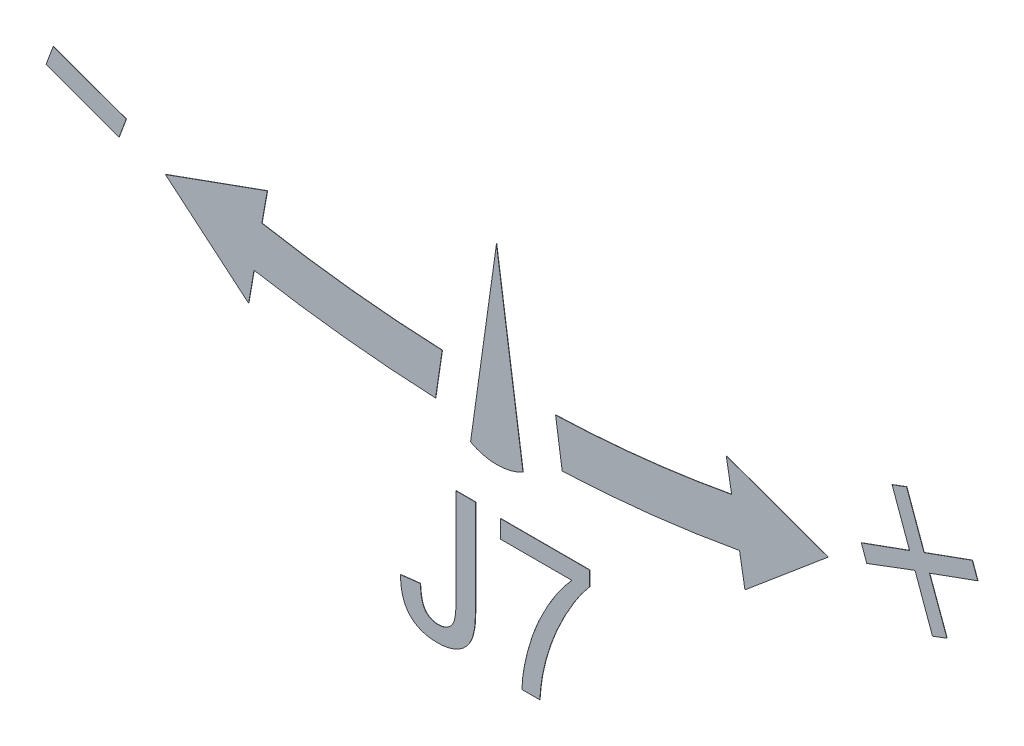
SolidWorks part; units mm, degrees
material "Air"
ref_plane "Front" through (0, 0, 0) normal (0, 0, 1) x (1, 0, 0)
ref_plane "Top" through (0, 0, 0) normal (0, 1, 0) x (1, 0, 0)
ref_plane "Right" through (0, 0, 0) normal (1, 0, 0) x (0, 0, -1)
sketch "Sketch1" plane through (0, 0, 0) normal (0, 0, 1) x (1, 0, 0)
  line L1616 (4481.7115, 1822.0394) -> (4481.7115, 1905.9102)
  line L1617 (4447.8406, 1780.6416) -> (4455.9051, 1781.1792)
  line L1618 (4455.9051, 1781.1792) -> (4464.5072, 1783.8674)
  line L1619 (4464.5072, 1783.8674) -> (4471.4964, 1788.7061)
  line L1620 (4471.4964, 1788.7061) -> (4476.8728, 1795.6953)
  line L1621 (4476.8728, 1795.6953) -> (4480.0986, 1803.7598)
  line L1622 (4480.0986, 1803.7598) -> (4481.1738, 1812.8996)
  line L1623 (4481.1738, 1812.8996) -> (4481.7115, 1822.0394)
  line L1624 (4415.0449, 1816.663) -> (4415.5826, 1809.1362)
  line L1625 (4415.5826, 1809.1362) -> (4416.6578, 1801.0717)
  line L1626 (4416.6578, 1801.0717) -> (4419.8836, 1794.0824)
  line L1627 (4419.8836, 1794.0824) -> (4424.7223, 1788.1685)
  line L1628 (4424.7223, 1788.1685) -> (4431.7116, 1783.8674)
  line L1629 (4431.7116, 1783.8674) -> (4439.2384, 1781.1792)
  line L1630 (4439.2384, 1781.1792) -> (4447.8406, 1780.6416)
  line L1631 (4432.2492, 1818.8136) -> (4415.0449, 1816.663)
  line L1632 (4448.3782, 1794.6201) -> (4444.0771, 1795.1577)
  line L1633 (4444.0771, 1795.1577) -> (4440.3137, 1796.7706)
  line L1634 (4440.3137, 1796.7706) -> (4437.6255, 1799.4588)
  line L1635 (4437.6255, 1799.4588) -> (4435.475, 1802.6846)
  line L1636 (4435.475, 1802.6846) -> (4433.3245, 1810.7491)
  line L1637 (4433.3245, 1810.7491) -> (4432.2492, 1818.8136)
  line L1638 (4463.9696, 1820.9641) -> (4463.9696, 1815.0501)
  line L1639 (4463.9696, 1815.0501) -> (4463.4319, 1809.1362)
  line L1640 (4463.4319, 1809.1362) -> (4462.3567, 1803.7598)
  line L1641 (4462.3567, 1803.7598) -> (4459.6685, 1799.9964)
  line L1642 (4459.6685, 1799.9964) -> (4456.4427, 1797.3082)
  line L1643 (4456.4427, 1797.3082) -> (4452.6793, 1795.1577)
  line L1644 (4452.6793, 1795.1577) -> (4448.3782, 1794.6201)
  line L1645 (4463.9696, 1905.9102) -> (4463.9696, 1820.9641)
  line L1646 (4481.7115, 1905.9102) -> (4463.9696, 1905.9102)
  line L1647 (4583.3242, 1891.3941) -> (4583.3242, 1904.2973)
  line L1648 (4544.0769, 1815.5878) -> (4552.1414, 1838.706)
  line L1649 (4552.1414, 1838.706) -> (4562.3565, 1860.2113)
  line L1650 (4562.3565, 1860.2113) -> (4572.0339, 1876.3403)
  line L1651 (4572.0339, 1876.3403) -> (4583.3242, 1891.3941)
  line L1652 (4538.7006, 1782.2545) -> (4540.8511, 1801.0717)
  line L1653 (4540.8511, 1801.0717) -> (4544.0769, 1815.5878)
  line L1654 (4523.1092, 1782.2545) -> (4538.7006, 1782.2545)
  line L1655 (4567.1952, 1888.7059) -> (4553.7543, 1870.964)
  line L1656 (4553.7543, 1870.964) -> (4543.0017, 1852.1468)
  line L1657 (4543.0017, 1852.1468) -> (4533.8619, 1832.2544)
  line L1658 (4533.8619, 1832.2544) -> (4528.4856, 1816.1254)
  line L1659 (4528.4856, 1816.1254) -> (4524.7221, 1799.4588)
  line L1660 (4524.7221, 1799.4588) -> (4523.1092, 1782.2545)
  line L1661 (4503.7544, 1888.7059) -> (4567.1952, 1888.7059)
  line L1662 (4503.7544, 1904.2973) -> (4503.7544, 1888.7059)
  line L1663 (4583.3242, 1904.2973) -> (4503.7544, 1904.2973)
  line L1664 (4098.3789, 2051.6088) -> (4163.4325, 2027.9529)
  line L1665 (4104.8305, 2068.8131) -> (4098.3789, 2051.6088)
  line L1666 (4169.8841, 2045.1572) -> (4104.8305, 2068.8131)
  line L1667 (4163.4325, 2027.9529) -> (4169.8841, 2045.1572)
  line L1668 (4852.6785, 2104.2969) -> (4868.2698, 2061.2862)
  line L1669 (4865.5817, 2109.1356) -> (4852.6785, 2104.2969)
  line L1670 (4881.173, 2066.1249) -> (4865.5817, 2109.1356)
  line L1671 (4924.1837, 2081.7163) -> (4881.173, 2066.1249)
  line L1672 (4929.0224, 2068.2754) -> (4924.1837, 2081.7163)
  line L1673 (4886.0117, 2052.6841) -> (4929.0224, 2068.2754)
  line L1674 (4901.6031, 2010.211) -> (4886.0117, 2052.6841)
  line L1675 (4888.6999, 2005.3723) -> (4901.6031, 2010.211)
  line L1676 (4873.1085, 2048.383) -> (4888.6999, 2005.3723)
  line L1677 (4830.0979, 2032.254) -> (4873.1085, 2048.383)
  line L1678 (4825.2592, 2045.6948) -> (4830.0979, 2032.254)
  line L1679 (4868.2698, 2061.2862) -> (4825.2592, 2045.6948)
  line L1680 (4476.8728, 1949.4585) -> (4477.4104, 1948.9208)
  line L1681 (4477.4104, 1948.9208) -> (4477.948, 1948.9208)
  line L1682 (4477.948, 1948.9208) -> (4478.4857, 1948.3832)
  line L1683 (4478.4857, 1948.3832) -> (4479.5609, 1948.3832)
  line L1684 (4479.5609, 1948.3832) -> (4480.0986, 1947.8456)
  line L1685 (4480.0986, 1947.8456) -> (4480.6362, 1947.8456)
  line L1686 (4480.6362, 1947.8456) -> (4481.1738, 1947.3079)
  line L1687 (4481.1738, 1947.3079) -> (4481.7115, 1947.3079)
  line L1688 (4481.7115, 1947.3079) -> (4482.7867, 1946.7703)
  line L1689 (4482.7867, 1946.7703) -> (4483.862, 1946.7703)
  line L1690 (4483.862, 1946.7703) -> (4484.3996, 1946.2327)
  line L1691 (4484.3996, 1946.2327) -> (4485.4749, 1946.2327)
  line L1692 (4485.4749, 1946.2327) -> (4486.0125, 1945.695)
  line L1693 (4486.0125, 1945.695) -> (4487.0878, 1945.695)
  line L1694 (4487.0878, 1945.695) -> (4487.6254, 1945.1574)
  line L1695 (4487.6254, 1945.1574) -> (4489.2383, 1945.1574)
  line L1696 (4489.2383, 1945.1574) -> (4489.776, 1944.6198)
  line L1697 (4489.776, 1944.6198) -> (4492.4641, 1944.6198)
  line L1698 (4492.4641, 1944.6198) -> (4493.0018, 1944.0821)
  line L1699 (4493.0018, 1944.0821) -> (4506.4426, 1944.0821)
  line L1700 (4506.4426, 1944.0821) -> (4506.9802, 1944.6198)
  line L1701 (4506.9802, 1944.6198) -> (4509.1308, 1944.6198)
  line L1702 (4509.1308, 1944.6198) -> (4510.206, 1945.1574)
  line L1703 (4510.206, 1945.1574) -> (4511.8189, 1945.1574)
  line L1704 (4511.8189, 1945.1574) -> (4512.3566, 1945.695)
  line L1705 (4512.3566, 1945.695) -> (4513.4318, 1945.695)
  line L1706 (4513.4318, 1945.695) -> (4513.9695, 1946.2327)
  line L1707 (4513.9695, 1946.2327) -> (4515.0447, 1946.2327)
  line L1708 (4515.0447, 1946.2327) -> (4515.5824, 1946.7703)
  line L1709 (4515.5824, 1946.7703) -> (4516.6576, 1946.7703)
  line L1710 (4516.6576, 1946.7703) -> (4517.1953, 1947.3079)
  line L1711 (4517.1953, 1947.3079) -> (4517.7329, 1947.3079)
  line L1712 (4517.7329, 1947.3079) -> (4518.2705, 1947.8456)
  line L1713 (4518.2705, 1947.8456) -> (4519.3458, 1947.8456)
  line L1714 (4519.3458, 1947.8456) -> (4519.8834, 1948.3832)
  line L1715 (4519.8834, 1948.3832) -> (4520.4211, 1948.3832)
  line L1716 (4520.4211, 1948.3832) -> (4520.9587, 1948.9208)
  line L1717 (4520.9587, 1948.9208) -> (4521.4963, 1948.9208)
  line L1718 (4521.4963, 1948.9208) -> (4522.034, 1949.4585)
  line L1719 (4522.034, 1949.4585) -> (4522.5716, 1949.4585)
  line L1720 (4522.5716, 1949.4585) -> (4523.1092, 1949.9961)
  line L1721 (4499.991, 2113.9743) -> (4476.8728, 1949.4585)
  line L1722 (4523.6469, 1949.4585) -> (4499.991, 2113.9743)
  line L1723 (4445.69, 1967.738) -> (4451.604, 2007.5229)
  line L1724 (4279.0237, 1957.523) -> (4283.8624, 1985.4799)
  line L1725 (4204.8303, 2019.8884) -> (4279.0237, 1957.523)
  line L1726 (4295.6903, 2052.6841) -> (4204.8303, 2019.8884)
  line L1727 (4290.8516, 2025.2648) -> (4295.6903, 2052.6841)
  line L1728 (4451.604, 2007.5229) -> (4436.5503, 2008.5981)
  line L1729 (4436.5503, 2008.5981) -> (4421.4965, 2009.1358)
  line L1730 (4421.4965, 2009.1358) -> (4406.9804, 2010.211)
  line L1731 (4406.9804, 2010.211) -> (4392.4643, 2011.8239)
  line L1732 (4392.4643, 2011.8239) -> (4377.4106, 2012.8992)
  line L1733 (4377.4106, 2012.8992) -> (4362.8945, 2014.5121)
  line L1734 (4362.8945, 2014.5121) -> (4347.8408, 2016.125)
  line L1735 (4347.8408, 2016.125) -> (4333.3247, 2018.2755)
  line L1736 (4333.3247, 2018.2755) -> (4318.8086, 2020.4261)
  line L1737 (4318.8086, 2020.4261) -> (4304.2925, 2022.5766)
  line L1738 (4304.2925, 2022.5766) -> (4290.314, 2025.2648)
  line L1739 (4283.8624, 1985.4799) -> (4298.9161, 1983.3294)
  line L1740 (4298.9161, 1983.3294) -> (4313.9699, 1980.6412)
  line L1741 (4313.9699, 1980.6412) -> (4329.0236, 1978.4907)
  line L1742 (4329.0236, 1978.4907) -> (4344.0773, 1976.8778)
  line L1743 (4344.0773, 1976.8778) -> (4359.1311, 1974.7272)
  line L1744 (4359.1311, 1974.7272) -> (4374.7224, 1973.1143)
  line L1745 (4374.7224, 1973.1143) -> (4389.7762, 1971.5014)
  line L1746 (4389.7762, 1971.5014) -> (4404.8299, 1970.4262)
  line L1747 (4404.8299, 1970.4262) -> (4420.4213, 1969.3509)
  line L1748 (4420.4213, 1969.3509) -> (4435.475, 1968.2756)
  line L1749 (4435.475, 1968.2756) -> (4445.69, 1968.2756)
  line L1750 (4704.8293, 2052.6841) -> (4709.668, 2025.2648)
  line L1751 (4552.6791, 2008.0605) -> (4558.593, 1967.738)
  line L1752 (4795.6893, 2019.8884) -> (4704.8293, 2052.6841)
  line L1753 (4709.668, 2025.2648) -> (4694.6143, 2023.1142)
  line L1754 (4694.6143, 2023.1142) -> (4680.0982, 2020.9637)
  line L1755 (4680.0982, 2020.9637) -> (4665.5821, 2018.8132)
  line L1756 (4665.5821, 2018.8132) -> (4651.066, 2016.6626)
  line L1757 (4651.066, 2016.6626) -> (4636.0122, 2015.0497)
  line L1758 (4636.0122, 2015.0497) -> (4621.4961, 2013.4368)
  line L1759 (4621.4961, 2013.4368) -> (4606.4424, 2011.8239)
  line L1760 (4606.4424, 2011.8239) -> (4591.9263, 2010.7487)
  line L1761 (4591.9263, 2010.7487) -> (4577.4102, 2009.6734)
  line L1762 (4577.4102, 2009.6734) -> (4562.3565, 2008.5981)
  line L1763 (4562.3565, 2008.5981) -> (4552.6791, 2008.0605)
  line L1764 (4716.6572, 1985.4799) -> (4721.4959, 1957.523)
  line L1765 (4558.593, 1967.738) -> (4573.6468, 1968.8133)
  line L1766 (4573.6468, 1968.8133) -> (4588.7005, 1969.8885)
  line L1767 (4588.7005, 1969.8885) -> (4604.2919, 1970.9638)
  line L1768 (4604.2919, 1970.9638) -> (4619.3456, 1972.5767)
  line L1769 (4619.3456, 1972.5767) -> (4634.3993, 1974.1896)
  line L1770 (4634.3993, 1974.1896) -> (4649.9907, 1975.8025)
  line L1771 (4649.9907, 1975.8025) -> (4665.0444, 1977.4154)
  line L1772 (4665.0444, 1977.4154) -> (4680.0982, 1979.5659)
  line L1773 (4680.0982, 1979.5659) -> (4695.1519, 1982.2541)
  line L1774 (4695.1519, 1982.2541) -> (4710.2056, 1984.4046)
  line L1775 (4710.2056, 1984.4046) -> (4716.6572, 1985.4799)
  line L1776 (4721.4959, 1957.523) -> (4795.6893, 2019.8884)
  line L7984 (4481.7115, 1822.0394) -> (4481.7115, 1905.9102)
  line L7985 (4481.7115, 1905.9102) -> (4463.9696, 1905.9102)
  line L7986 (4463.9696, 1905.9102) -> (4463.9696, 1811.2867)
  line L7987 (4463.9696, 1811.2867) -> (4463.4319, 1809.6738)
  line L7988 (4463.4319, 1809.6738) -> (4463.4319, 1807.5233)
  line L7989 (4463.4319, 1807.5233) -> (4462.8943, 1805.9104)
  line L7990 (4462.8943, 1805.9104) -> (4462.3567, 1804.8351)
  line L7991 (4462.3567, 1804.8351) -> (4462.3567, 1803.7598)
  line L7992 (4462.3567, 1803.7598) -> (4461.819, 1802.6846)
  line L7993 (4461.819, 1802.6846) -> (4461.2814, 1801.6093)
  line L7994 (4461.2814, 1801.6093) -> (4460.7438, 1801.0717)
  line L7995 (4460.7438, 1801.0717) -> (4459.6685, 1799.9964)
  line L7996 (4459.6685, 1799.9964) -> (4459.1309, 1798.9211)
  line L7997 (4459.1309, 1798.9211) -> (4458.5932, 1798.3835)
  line L7998 (4458.5932, 1798.3835) -> (4457.518, 1797.8459)
  line L7999 (4457.518, 1797.8459) -> (4456.4427, 1797.3082)
  line L8000 (4456.4427, 1797.3082) -> (4455.3674, 1796.7706)
  line L8001 (4455.3674, 1796.7706) -> (4454.2922, 1796.233)
  line L8002 (4454.2922, 1796.233) -> (4453.2169, 1795.6953)
  line L8003 (4453.2169, 1795.6953) -> (4452.1416, 1795.1577)
  line L8004 (4452.1416, 1795.1577) -> (4449.4535, 1795.1577)
  line L8005 (4449.4535, 1795.1577) -> (4448.3782, 1794.6201)
  line L8006 (4448.3782, 1794.6201) -> (4447.3029, 1795.1577)
  line L8007 (4447.3029, 1795.1577) -> (4444.6148, 1795.1577)
  line L8008 (4444.6148, 1795.1577) -> (4443.5395, 1795.6953)
  line L8009 (4443.5395, 1795.6953) -> (4442.4642, 1795.6953)
  line L8010 (4442.4642, 1795.6953) -> (4441.389, 1796.233)
  line L8011 (4441.389, 1796.233) -> (4440.3137, 1796.7706)
  line L8012 (4440.3137, 1796.7706) -> (4439.7761, 1797.3082)
  line L8013 (4439.7761, 1797.3082) -> (4438.7008, 1798.3835)
  line L8014 (4438.7008, 1798.3835) -> (4437.6255, 1798.9211)
  line L8015 (4437.6255, 1798.9211) -> (4437.0879, 1799.9964)
  line L8016 (4437.0879, 1799.9964) -> (4436.5503, 1801.0717)
  line L8017 (4436.5503, 1801.0717) -> (4436.0126, 1801.6093)
  line L8018 (4436.0126, 1801.6093) -> (4435.475, 1802.6846)
  line L8019 (4435.475, 1802.6846) -> (4434.9374, 1804.2975)
  line L8020 (4434.9374, 1804.2975) -> (4434.3997, 1805.9104)
  line L8021 (4434.3997, 1805.9104) -> (4433.8621, 1806.9856)
  line L8022 (4433.8621, 1806.9856) -> (4433.3245, 1808.5985)
  line L8023 (4433.3245, 1808.5985) -> (4433.3245, 1810.2114)
  line L8024 (4433.3245, 1810.2114) -> (4432.7868, 1811.8243)
  line L8025 (4432.7868, 1811.8243) -> (4432.7868, 1816.1254)
  line L8026 (4432.7868, 1816.1254) -> (4432.2492, 1818.8136)
  line L8027 (4432.2492, 1818.8136) -> (4415.0449, 1816.663)
  line L8028 (4415.0449, 1816.663) -> (4415.0449, 1809.1362)
  line L8029 (4415.0449, 1809.1362) -> (4415.5826, 1806.9856)
  line L8030 (4415.5826, 1806.9856) -> (4416.1202, 1804.2975)
  line L8031 (4416.1202, 1804.2975) -> (4416.6578, 1801.6093)
  line L8032 (4416.6578, 1801.6093) -> (4417.1955, 1799.4588)
  line L8033 (4417.1955, 1799.4588) -> (4418.2707, 1797.8459)
  line L8034 (4418.2707, 1797.8459) -> (4418.8084, 1795.6953)
  line L8035 (4418.8084, 1795.6953) -> (4419.8836, 1794.0824)
  line L8036 (4419.8836, 1794.0824) -> (4420.9589, 1792.4695)
  line L8037 (4420.9589, 1792.4695) -> (4422.0342, 1790.8566)
  line L8038 (4422.0342, 1790.8566) -> (4423.1094, 1789.2437)
  line L8039 (4423.1094, 1789.2437) -> (4424.7223, 1788.1685)
  line L8040 (4424.7223, 1788.1685) -> (4426.3352, 1786.5556)
  line L8041 (4426.3352, 1786.5556) -> (4427.9481, 1785.4803)
  line L8042 (4427.9481, 1785.4803) -> (4429.561, 1784.405)
  line L8043 (4429.561, 1784.405) -> (4431.1739, 1783.8674)
  line L8044 (4431.1739, 1783.8674) -> (4433.3245, 1782.7921)
  line L8045 (4433.3245, 1782.7921) -> (4434.9374, 1782.2545)
  line L8046 (4434.9374, 1782.2545) -> (4437.0879, 1781.7169)
  line L8047 (4437.0879, 1781.7169) -> (4439.2384, 1781.1792)
  line L8048 (4439.2384, 1781.1792) -> (4441.389, 1781.1792)
  line L8049 (4441.389, 1781.1792) -> (4443.5395, 1780.6416)
  line L8050 (4443.5395, 1780.6416) -> (4452.1416, 1780.6416)
  line L8051 (4452.1416, 1780.6416) -> (4454.2922, 1781.1792)
  line L8052 (4454.2922, 1781.1792) -> (4456.4427, 1781.1792)
  line L8053 (4456.4427, 1781.1792) -> (4458.0556, 1781.7169)
  line L8054 (4458.0556, 1781.7169) -> (4460.2061, 1782.2545)
  line L8055 (4460.2061, 1782.2545) -> (4462.3567, 1783.3298)
  line L8056 (4462.3567, 1783.3298) -> (4464.5072, 1783.8674)
  line L8057 (4464.5072, 1783.8674) -> (4466.1201, 1784.9427)
  line L8058 (4466.1201, 1784.9427) -> (4468.2706, 1786.0179)
  line L8059 (4468.2706, 1786.0179) -> (4469.8835, 1787.0932)
  line L8060 (4469.8835, 1787.0932) -> (4471.4964, 1788.7061)
  line L8061 (4471.4964, 1788.7061) -> (4473.1093, 1790.319)
  line L8062 (4473.1093, 1790.319) -> (4474.1846, 1791.9319)
  line L8063 (4474.1846, 1791.9319) -> (4475.7975, 1793.5448)
  line L8064 (4475.7975, 1793.5448) -> (4476.8728, 1795.6953)
  line L8065 (4476.8728, 1795.6953) -> (4477.948, 1797.3082)
  line L8066 (4477.948, 1797.3082) -> (4478.4857, 1799.4588)
  line L8067 (4478.4857, 1799.4588) -> (4479.0233, 1801.6093)
  line L8068 (4479.0233, 1801.6093) -> (4480.0986, 1803.7598)
  line L8069 (4480.0986, 1803.7598) -> (4480.0986, 1805.9104)
  line L8070 (4480.0986, 1805.9104) -> (4480.6362, 1808.0609)
  line L8071 (4480.6362, 1808.0609) -> (4481.1738, 1810.2114)
  line L8072 (4481.1738, 1810.2114) -> (4481.1738, 1812.8996)
  line L8073 (4481.1738, 1812.8996) -> (4481.7115, 1816.1254)
  line L8074 (4481.7115, 1816.1254) -> (4481.7115, 1822.0394)
  line L8075 (4481.7115, 1822.0394) -> (4481.7115, 1905.9102)
  line L8076 (4481.7115, 1905.9102) -> (4463.9696, 1905.9102)
  line L8077 (4463.9696, 1905.9102) -> (4463.9696, 1811.2867)
  line L8078 (4463.9696, 1811.2867) -> (4463.4319, 1809.6738)
  line L8079 (4463.4319, 1809.6738) -> (4463.4319, 1807.5233)
  line L8080 (4463.4319, 1807.5233) -> (4462.8943, 1805.9104)
  line L8081 (4462.8943, 1805.9104) -> (4462.3567, 1804.8351)
  line L8082 (4462.3567, 1804.8351) -> (4462.3567, 1803.7598)
  line L8083 (4462.3567, 1803.7598) -> (4461.819, 1802.6846)
  line L8084 (4461.819, 1802.6846) -> (4461.2814, 1801.6093)
  line L8085 (4461.2814, 1801.6093) -> (4460.7438, 1801.0717)
  line L8086 (4460.7438, 1801.0717) -> (4459.6685, 1799.9964)
  line L8087 (4459.6685, 1799.9964) -> (4459.1309, 1798.9211)
  line L8088 (4459.1309, 1798.9211) -> (4458.5932, 1798.3835)
  line L8089 (4458.5932, 1798.3835) -> (4457.518, 1797.8459)
  line L8090 (4457.518, 1797.8459) -> (4456.4427, 1797.3082)
  line L8091 (4456.4427, 1797.3082) -> (4455.3674, 1796.7706)
  line L8092 (4455.3674, 1796.7706) -> (4454.2922, 1796.233)
  line L8093 (4454.2922, 1796.233) -> (4453.2169, 1795.6953)
  line L8094 (4453.2169, 1795.6953) -> (4452.1416, 1795.1577)
  line L8095 (4452.1416, 1795.1577) -> (4449.4535, 1795.1577)
  line L8096 (4449.4535, 1795.1577) -> (4448.3782, 1794.6201)
  line L8097 (4448.3782, 1794.6201) -> (4447.3029, 1795.1577)
  line L8098 (4447.3029, 1795.1577) -> (4444.6148, 1795.1577)
  line L8099 (4444.6148, 1795.1577) -> (4443.5395, 1795.6953)
  line L8100 (4443.5395, 1795.6953) -> (4442.4642, 1795.6953)
  line L8101 (4442.4642, 1795.6953) -> (4441.389, 1796.233)
  line L8102 (4441.389, 1796.233) -> (4440.3137, 1796.7706)
  line L8103 (4440.3137, 1796.7706) -> (4439.7761, 1797.3082)
  line L8104 (4439.7761, 1797.3082) -> (4438.7008, 1798.3835)
  line L8105 (4438.7008, 1798.3835) -> (4437.6255, 1798.9211)
  line L8106 (4437.6255, 1798.9211) -> (4437.0879, 1799.9964)
  line L8107 (4437.0879, 1799.9964) -> (4436.5503, 1801.0717)
  line L8108 (4436.5503, 1801.0717) -> (4436.0126, 1801.6093)
  line L8109 (4436.0126, 1801.6093) -> (4435.475, 1802.6846)
  line L8110 (4435.475, 1802.6846) -> (4434.9374, 1804.2975)
  line L8111 (4434.9374, 1804.2975) -> (4434.3997, 1805.9104)
  line L8112 (4434.3997, 1805.9104) -> (4433.8621, 1806.9856)
  line L8113 (4433.8621, 1806.9856) -> (4433.3245, 1808.5985)
  line L8114 (4433.3245, 1808.5985) -> (4433.3245, 1810.2114)
  line L8115 (4433.3245, 1810.2114) -> (4432.7868, 1811.8243)
  line L8116 (4432.7868, 1811.8243) -> (4432.7868, 1816.1254)
  line L8117 (4432.7868, 1816.1254) -> (4432.2492, 1818.8136)
  line L8118 (4432.2492, 1818.8136) -> (4415.0449, 1816.663)
  line L8119 (4415.0449, 1816.663) -> (4415.0449, 1809.1362)
  line L8120 (4415.0449, 1809.1362) -> (4415.5826, 1806.9856)
  line L8121 (4415.5826, 1806.9856) -> (4416.1202, 1804.2975)
  line L8122 (4416.1202, 1804.2975) -> (4416.6578, 1801.6093)
  line L8123 (4416.6578, 1801.6093) -> (4417.1955, 1799.4588)
  line L8124 (4417.1955, 1799.4588) -> (4418.2707, 1797.8459)
  line L8125 (4418.2707, 1797.8459) -> (4418.8084, 1795.6953)
  line L8126 (4418.8084, 1795.6953) -> (4419.8836, 1794.0824)
  line L8127 (4419.8836, 1794.0824) -> (4420.9589, 1792.4695)
  line L8128 (4420.9589, 1792.4695) -> (4422.0342, 1790.8566)
  line L8129 (4422.0342, 1790.8566) -> (4423.1094, 1789.2437)
  line L8130 (4423.1094, 1789.2437) -> (4424.7223, 1788.1685)
  line L8131 (4424.7223, 1788.1685) -> (4426.3352, 1786.5556)
  line L8132 (4426.3352, 1786.5556) -> (4427.9481, 1785.4803)
  line L8133 (4427.9481, 1785.4803) -> (4429.561, 1784.405)
  line L8134 (4429.561, 1784.405) -> (4431.1739, 1783.8674)
  line L8135 (4431.1739, 1783.8674) -> (4433.3245, 1782.7921)
  line L8136 (4433.3245, 1782.7921) -> (4434.9374, 1782.2545)
  line L8137 (4434.9374, 1782.2545) -> (4437.0879, 1781.7169)
  line L8138 (4437.0879, 1781.7169) -> (4439.2384, 1781.1792)
  line L8139 (4439.2384, 1781.1792) -> (4441.389, 1781.1792)
  line L8140 (4441.389, 1781.1792) -> (4443.5395, 1780.6416)
  line L8141 (4443.5395, 1780.6416) -> (4452.1416, 1780.6416)
  line L8142 (4452.1416, 1780.6416) -> (4454.2922, 1781.1792)
  line L8143 (4454.2922, 1781.1792) -> (4456.4427, 1781.1792)
  line L8144 (4456.4427, 1781.1792) -> (4458.0556, 1781.7169)
  line L8145 (4458.0556, 1781.7169) -> (4460.2061, 1782.2545)
  line L8146 (4460.2061, 1782.2545) -> (4462.3567, 1783.3298)
  line L8147 (4462.3567, 1783.3298) -> (4464.5072, 1783.8674)
  line L8148 (4464.5072, 1783.8674) -> (4466.1201, 1784.9427)
  line L8149 (4466.1201, 1784.9427) -> (4468.2706, 1786.0179)
  line L8150 (4468.2706, 1786.0179) -> (4469.8835, 1787.0932)
  line L8151 (4469.8835, 1787.0932) -> (4471.4964, 1788.7061)
  line L8152 (4471.4964, 1788.7061) -> (4473.1093, 1790.319)
  line L8153 (4473.1093, 1790.319) -> (4474.1846, 1791.9319)
  line L8154 (4474.1846, 1791.9319) -> (4475.7975, 1793.5448)
  line L8155 (4475.7975, 1793.5448) -> (4476.8728, 1795.6953)
  line L8156 (4476.8728, 1795.6953) -> (4477.948, 1797.3082)
  line L8157 (4477.948, 1797.3082) -> (4478.4857, 1799.4588)
  line L8158 (4478.4857, 1799.4588) -> (4479.0233, 1801.6093)
  line L8159 (4479.0233, 1801.6093) -> (4480.0986, 1803.7598)
  line L8160 (4480.0986, 1803.7598) -> (4480.0986, 1805.9104)
  line L8161 (4480.0986, 1805.9104) -> (4480.6362, 1808.0609)
  line L8162 (4480.6362, 1808.0609) -> (4481.1738, 1810.2114)
  line L8163 (4481.1738, 1810.2114) -> (4481.1738, 1812.8996)
  line L8164 (4481.1738, 1812.8996) -> (4481.7115, 1816.1254)
  line L8165 (4481.7115, 1816.1254) -> (4481.7115, 1822.0394)
  line L8166 (4583.3242, 1891.3941) -> (4583.3242, 1904.2973)
  line L8167 (4583.3242, 1904.2973) -> (4503.7544, 1904.2973)
  line L8168 (4503.7544, 1904.2973) -> (4503.7544, 1888.7059)
  line L8169 (4503.7544, 1888.7059) -> (4567.1952, 1888.7059)
  line L8170 (4567.1952, 1888.7059) -> (4562.3565, 1882.7919)
  line L8171 (4562.3565, 1882.7919) -> (4558.0554, 1876.878)
  line L8172 (4558.0554, 1876.878) -> (4553.7543, 1870.964)
  line L8173 (4553.7543, 1870.964) -> (4549.9909, 1865.05)
  line L8174 (4549.9909, 1865.05) -> (4546.2275, 1858.5984)
  line L8175 (4546.2275, 1858.5984) -> (4542.464, 1852.1468)
  line L8176 (4542.464, 1852.1468) -> (4539.2382, 1845.6952)
  line L8177 (4539.2382, 1845.6952) -> (4536.5501, 1839.2436)
  line L8178 (4536.5501, 1839.2436) -> (4533.8619, 1832.2544)
  line L8179 (4533.8619, 1832.2544) -> (4531.7114, 1826.3404)
  line L8180 (4531.7114, 1826.3404) -> (4529.5608, 1820.4265)
  line L8181 (4529.5608, 1820.4265) -> (4527.9479, 1813.9749)
  line L8182 (4527.9479, 1813.9749) -> (4526.335, 1807.5233)
  line L8183 (4526.335, 1807.5233) -> (4525.2598, 1801.6093)
  line L8184 (4525.2598, 1801.6093) -> (4524.1845, 1795.1577)
  line L8185 (4524.1845, 1795.1577) -> (4523.1092, 1788.7061)
  line L8186 (4523.1092, 1788.7061) -> (4523.1092, 1782.2545)
  line L8187 (4523.1092, 1782.2545) -> (4538.7006, 1782.2545)
  line L8188 (4538.7006, 1782.2545) -> (4539.2382, 1786.0179)
  line L8189 (4539.2382, 1786.0179) -> (4539.2382, 1789.7814)
  line L8190 (4539.2382, 1789.7814) -> (4539.7759, 1793.5448)
  line L8191 (4539.7759, 1793.5448) -> (4540.3135, 1797.3082)
  line L8192 (4540.3135, 1797.3082) -> (4540.8511, 1801.0717)
  line L8193 (4540.8511, 1801.0717) -> (4541.9264, 1804.8351)
  line L8194 (4541.9264, 1804.8351) -> (4542.464, 1808.5985)
  line L8195 (4542.464, 1808.5985) -> (4543.5393, 1812.362)
  line L8196 (4543.5393, 1812.362) -> (4544.0769, 1815.5878)
  line L8197 (4544.0769, 1815.5878) -> (4546.2275, 1822.577)
  line L8198 (4546.2275, 1822.577) -> (4548.378, 1829.0286)
  line L8199 (4548.378, 1829.0286) -> (4550.5285, 1835.4802)
  line L8200 (4550.5285, 1835.4802) -> (4553.2167, 1841.9318)
  line L8201 (4553.2167, 1841.9318) -> (4555.9049, 1847.8458)
  line L8202 (4555.9049, 1847.8458) -> (4559.1307, 1854.2974)
  line L8203 (4559.1307, 1854.2974) -> (4562.3565, 1860.2113)
  line L8204 (4562.3565, 1860.2113) -> (4565.5823, 1865.5877)
  line L8205 (4565.5823, 1865.5877) -> (4568.2704, 1870.964)
  line L8206 (4568.2704, 1870.964) -> (4572.0339, 1876.3403)
  line L8207 (4572.0339, 1876.3403) -> (4575.2597, 1881.7167)
  line L8208 (4575.2597, 1881.7167) -> (4579.0231, 1886.5554)
  line L8209 (4579.0231, 1886.5554) -> (4583.3242, 1891.3941)
  line L8210 (4583.3242, 1891.3941) -> (4583.3242, 1904.2973)
  line L8211 (4583.3242, 1904.2973) -> (4503.7544, 1904.2973)
  line L8212 (4503.7544, 1904.2973) -> (4503.7544, 1888.7059)
  line L8213 (4503.7544, 1888.7059) -> (4567.1952, 1888.7059)
  line L8214 (4567.1952, 1888.7059) -> (4562.3565, 1882.7919)
  line L8215 (4562.3565, 1882.7919) -> (4558.0554, 1876.878)
  line L8216 (4558.0554, 1876.878) -> (4553.7543, 1870.964)
  line L8217 (4553.7543, 1870.964) -> (4549.9909, 1865.05)
  line L8218 (4549.9909, 1865.05) -> (4546.2275, 1858.5984)
  line L8219 (4546.2275, 1858.5984) -> (4542.464, 1852.1468)
  line L8220 (4542.464, 1852.1468) -> (4539.2382, 1845.6952)
  line L8221 (4539.2382, 1845.6952) -> (4536.5501, 1839.2436)
  line L8222 (4536.5501, 1839.2436) -> (4533.8619, 1832.2544)
  line L8223 (4533.8619, 1832.2544) -> (4531.7114, 1826.3404)
  line L8224 (4531.7114, 1826.3404) -> (4529.5608, 1820.4265)
  line L8225 (4529.5608, 1820.4265) -> (4527.9479, 1813.9749)
  line L8226 (4527.9479, 1813.9749) -> (4526.335, 1807.5233)
  line L8227 (4526.335, 1807.5233) -> (4525.2598, 1801.6093)
  line L8228 (4525.2598, 1801.6093) -> (4524.1845, 1795.1577)
  line L8229 (4524.1845, 1795.1577) -> (4523.1092, 1788.7061)
  line L8230 (4523.1092, 1788.7061) -> (4523.1092, 1782.2545)
  line L8231 (4523.1092, 1782.2545) -> (4538.7006, 1782.2545)
  line L8232 (4538.7006, 1782.2545) -> (4539.2382, 1786.0179)
  line L8233 (4539.2382, 1786.0179) -> (4539.2382, 1789.7814)
  line L8234 (4539.2382, 1789.7814) -> (4539.7759, 1793.5448)
  line L8235 (4539.7759, 1793.5448) -> (4540.3135, 1797.3082)
  line L8236 (4540.3135, 1797.3082) -> (4540.8511, 1801.0717)
  line L8237 (4540.8511, 1801.0717) -> (4541.9264, 1804.8351)
  line L8238 (4541.9264, 1804.8351) -> (4542.464, 1808.5985)
  line L8239 (4542.464, 1808.5985) -> (4543.5393, 1812.362)
  line L8240 (4543.5393, 1812.362) -> (4544.0769, 1815.5878)
  line L8241 (4544.0769, 1815.5878) -> (4546.2275, 1822.577)
  line L8242 (4546.2275, 1822.577) -> (4548.378, 1829.0286)
  line L8243 (4548.378, 1829.0286) -> (4550.5285, 1835.4802)
  line L8244 (4550.5285, 1835.4802) -> (4553.2167, 1841.9318)
  line L8245 (4553.2167, 1841.9318) -> (4555.9049, 1847.8458)
  line L8246 (4555.9049, 1847.8458) -> (4559.1307, 1854.2974)
  line L8247 (4559.1307, 1854.2974) -> (4562.3565, 1860.2113)
  line L8248 (4562.3565, 1860.2113) -> (4565.5823, 1865.5877)
  line L8249 (4565.5823, 1865.5877) -> (4568.2704, 1870.964)
  line L8250 (4568.2704, 1870.964) -> (4572.0339, 1876.3403)
  line L8251 (4572.0339, 1876.3403) -> (4575.2597, 1881.7167)
  line L8252 (4575.2597, 1881.7167) -> (4579.0231, 1886.5554)
  line L8253 (4579.0231, 1886.5554) -> (4583.3242, 1891.3941)
  line L8254 (4852.6785, 2104.2969) -> (4868.2698, 2061.2862)
  line L8255 (4868.2698, 2061.2862) -> (4825.2592, 2045.6948)
  line L8256 (4825.2592, 2045.6948) -> (4830.0979, 2032.254)
  line L8257 (4830.0979, 2032.254) -> (4873.1085, 2048.383)
  line L8258 (4873.1085, 2048.383) -> (4888.6999, 2005.3723)
  line L8259 (4888.6999, 2005.3723) -> (4901.6031, 2010.211)
  line L8260 (4901.6031, 2010.211) -> (4886.0117, 2052.6841)
  line L8261 (4886.0117, 2052.6841) -> (4929.0224, 2068.2754)
  line L8262 (4929.0224, 2068.2754) -> (4924.1837, 2081.7163)
  line L8263 (4924.1837, 2081.7163) -> (4881.173, 2066.1249)
  line L8264 (4881.173, 2066.1249) -> (4865.5817, 2109.1356)
  line L8265 (4865.5817, 2109.1356) -> (4852.6785, 2104.2969)
  line L8266 (4852.6785, 2104.2969) -> (4868.2698, 2061.2862)
  line L8267 (4868.2698, 2061.2862) -> (4825.2592, 2045.6948)
  line L8268 (4825.2592, 2045.6948) -> (4830.0979, 2032.254)
  line L8269 (4830.0979, 2032.254) -> (4873.1085, 2048.383)
  line L8270 (4873.1085, 2048.383) -> (4888.6999, 2005.3723)
  line L8271 (4888.6999, 2005.3723) -> (4901.6031, 2010.211)
  line L8272 (4901.6031, 2010.211) -> (4886.0117, 2052.6841)
  line L8273 (4886.0117, 2052.6841) -> (4929.0224, 2068.2754)
  line L8274 (4929.0224, 2068.2754) -> (4924.1837, 2081.7163)
  line L8275 (4924.1837, 2081.7163) -> (4881.173, 2066.1249)
  line L8276 (4881.173, 2066.1249) -> (4865.5817, 2109.1356)
  line L8277 (4865.5817, 2109.1356) -> (4852.6785, 2104.2969)
  line L8278 (4098.3789, 2051.6088) -> (4163.4325, 2027.9529)
  line L8279 (4163.4325, 2027.9529) -> (4169.8841, 2045.1572)
  line L8280 (4169.8841, 2045.1572) -> (4104.8305, 2068.8131)
  line L8281 (4104.8305, 2068.8131) -> (4098.3789, 2051.6088)
  line L8282 (4098.3789, 2051.6088) -> (4163.4325, 2027.9529)
  line L8283 (4163.4325, 2027.9529) -> (4169.8841, 2045.1572)
  line L8284 (4169.8841, 2045.1572) -> (4104.8305, 2068.8131)
  line L8285 (4104.8305, 2068.8131) -> (4098.3789, 2051.6088)
  line L8286 (4445.69, 1967.738) -> (4451.604, 2007.5229)
  line L8287 (4451.604, 2007.5229) -> (4436.5503, 2008.5981)
  line L8288 (4436.5503, 2008.5981) -> (4422.0342, 2009.1358)
  line L8289 (4422.0342, 2009.1358) -> (4407.5181, 2010.211)
  line L8290 (4407.5181, 2010.211) -> (4393.002, 2011.2863)
  line L8291 (4393.002, 2011.2863) -> (4377.9482, 2012.8992)
  line L8292 (4377.9482, 2012.8992) -> (4363.4321, 2014.5121)
  line L8293 (4363.4321, 2014.5121) -> (4348.916, 2016.125)
  line L8294 (4348.916, 2016.125) -> (4334.3999, 2018.2755)
  line L8295 (4334.3999, 2018.2755) -> (4319.8838, 2020.4261)
  line L8296 (4319.8838, 2020.4261) -> (4305.3677, 2022.5766)
  line L8297 (4305.3677, 2022.5766) -> (4290.8516, 2025.2648)
  line L8298 (4290.8516, 2025.2648) -> (4295.6903, 2052.6841)
  line L8299 (4295.6903, 2052.6841) -> (4204.8303, 2019.8884)
  line L8300 (4204.8303, 2019.8884) -> (4279.0237, 1957.523)
  line L8301 (4279.0237, 1957.523) -> (4283.8624, 1985.4799)
  line L8302 (4283.8624, 1985.4799) -> (4298.3785, 1982.7917)
  line L8303 (4298.3785, 1982.7917) -> (4312.8946, 1980.6412)
  line L8304 (4312.8946, 1980.6412) -> (4327.4107, 1978.4907)
  line L8305 (4327.4107, 1978.4907) -> (4342.4644, 1976.3401)
  line L8306 (4342.4644, 1976.3401) -> (4356.9805, 1974.7272)
  line L8307 (4356.9805, 1974.7272) -> (4372.0343, 1973.1143)
  line L8308 (4372.0343, 1973.1143) -> (4386.5504, 1971.5014)
  line L8309 (4386.5504, 1971.5014) -> (4401.6041, 1970.4262)
  line L8310 (4401.6041, 1970.4262) -> (4416.1202, 1969.3509)
  line L8311 (4416.1202, 1969.3509) -> (4431.1739, 1968.2756)
  line L8312 (4431.1739, 1968.2756) -> (4445.69, 1967.738)
  line L8313 (4445.69, 1967.738) -> (4451.604, 2007.5229)
  line L8314 (4451.604, 2007.5229) -> (4436.5503, 2008.5981)
  line L8315 (4436.5503, 2008.5981) -> (4422.0342, 2009.1358)
  line L8316 (4422.0342, 2009.1358) -> (4407.5181, 2010.211)
  line L8317 (4407.5181, 2010.211) -> (4393.002, 2011.2863)
  line L8318 (4393.002, 2011.2863) -> (4377.9482, 2012.8992)
  line L8319 (4377.9482, 2012.8992) -> (4363.4321, 2014.5121)
  line L8320 (4363.4321, 2014.5121) -> (4348.916, 2016.125)
  line L8321 (4348.916, 2016.125) -> (4334.3999, 2018.2755)
  line L8322 (4334.3999, 2018.2755) -> (4319.8838, 2020.4261)
  line L8323 (4319.8838, 2020.4261) -> (4305.3677, 2022.5766)
  line L8324 (4305.3677, 2022.5766) -> (4290.8516, 2025.2648)
  line L8325 (4290.8516, 2025.2648) -> (4295.6903, 2052.6841)
  line L8326 (4295.6903, 2052.6841) -> (4204.8303, 2019.8884)
  line L8327 (4204.8303, 2019.8884) -> (4279.0237, 1957.523)
  line L8328 (4279.0237, 1957.523) -> (4283.8624, 1985.4799)
  line L8329 (4283.8624, 1985.4799) -> (4298.3785, 1982.7917)
  line L8330 (4298.3785, 1982.7917) -> (4312.8946, 1980.6412)
  line L8331 (4312.8946, 1980.6412) -> (4327.4107, 1978.4907)
  line L8332 (4327.4107, 1978.4907) -> (4342.4644, 1976.3401)
  line L8333 (4342.4644, 1976.3401) -> (4356.9805, 1974.7272)
  line L8334 (4356.9805, 1974.7272) -> (4372.0343, 1973.1143)
  line L8335 (4372.0343, 1973.1143) -> (4386.5504, 1971.5014)
  line L8336 (4386.5504, 1971.5014) -> (4401.6041, 1970.4262)
  line L8337 (4401.6041, 1970.4262) -> (4416.1202, 1969.3509)
  line L8338 (4416.1202, 1969.3509) -> (4431.1739, 1968.2756)
  line L8339 (4431.1739, 1968.2756) -> (4445.69, 1967.738)
  line L8340 (4552.6791, 2008.0605) -> (4558.593, 1967.738)
  line L8341 (4558.593, 1967.738) -> (4573.1091, 1968.2756)
  line L8342 (4573.1091, 1968.2756) -> (4587.6252, 1969.3509)
  line L8343 (4587.6252, 1969.3509) -> (4601.6037, 1970.4262)
  line L8344 (4601.6037, 1970.4262) -> (4616.1198, 1972.0391)
  line L8345 (4616.1198, 1972.0391) -> (4630.6359, 1973.1143)
  line L8346 (4630.6359, 1973.1143) -> (4645.152, 1974.7272)
  line L8347 (4645.152, 1974.7272) -> (4659.6681, 1976.3401)
  line L8348 (4659.6681, 1976.3401) -> (4673.6466, 1978.4907)
  line L8349 (4673.6466, 1978.4907) -> (4688.1627, 1980.6412)
  line L8350 (4688.1627, 1980.6412) -> (4702.6788, 1982.7917)
  line L8351 (4702.6788, 1982.7917) -> (4716.6572, 1985.4799)
  line L8352 (4716.6572, 1985.4799) -> (4721.4959, 1957.523)
  line L8353 (4721.4959, 1957.523) -> (4795.6893, 2019.8884)
  line L8354 (4795.6893, 2019.8884) -> (4704.8293, 2052.6841)
  line L8355 (4704.8293, 2052.6841) -> (4709.668, 2025.2648)
  line L8356 (4709.668, 2025.2648) -> (4695.6895, 2022.5766)
  line L8357 (4695.6895, 2022.5766) -> (4681.1734, 2020.4261)
  line L8358 (4681.1734, 2020.4261) -> (4667.195, 2018.2755)
  line L8359 (4667.195, 2018.2755) -> (4653.2165, 2016.6626)
  line L8360 (4653.2165, 2016.6626) -> (4638.7004, 2014.5121)
  line L8361 (4638.7004, 2014.5121) -> (4624.1843, 2012.8992)
  line L8362 (4624.1843, 2012.8992) -> (4610.2058, 2011.8239)
  line L8363 (4610.2058, 2011.8239) -> (4595.6897, 2010.7487)
  line L8364 (4595.6897, 2010.7487) -> (4581.7113, 2009.6734)
  line L8365 (4581.7113, 2009.6734) -> (4567.1952, 2008.5981)
  line L8366 (4567.1952, 2008.5981) -> (4552.6791, 2008.0605)
  line L8367 (4552.6791, 2008.0605) -> (4558.593, 1967.738)
  line L8368 (4558.593, 1967.738) -> (4573.1091, 1968.2756)
  line L8369 (4573.1091, 1968.2756) -> (4587.6252, 1969.3509)
  line L8370 (4587.6252, 1969.3509) -> (4601.6037, 1970.4262)
  line L8371 (4601.6037, 1970.4262) -> (4616.1198, 1972.0391)
  line L8372 (4616.1198, 1972.0391) -> (4630.6359, 1973.1143)
  line L8373 (4630.6359, 1973.1143) -> (4645.152, 1974.7272)
  line L8374 (4645.152, 1974.7272) -> (4659.6681, 1976.3401)
  line L8375 (4659.6681, 1976.3401) -> (4673.6466, 1978.4907)
  line L8376 (4673.6466, 1978.4907) -> (4688.1627, 1980.6412)
  line L8377 (4688.1627, 1980.6412) -> (4702.6788, 1982.7917)
  line L8378 (4702.6788, 1982.7917) -> (4716.6572, 1985.4799)
  line L8379 (4716.6572, 1985.4799) -> (4721.4959, 1957.523)
  line L8380 (4721.4959, 1957.523) -> (4795.6893, 2019.8884)
  line L8381 (4795.6893, 2019.8884) -> (4704.8293, 2052.6841)
  line L8382 (4704.8293, 2052.6841) -> (4709.668, 2025.2648)
  line L8383 (4709.668, 2025.2648) -> (4695.6895, 2022.5766)
  line L8384 (4695.6895, 2022.5766) -> (4681.1734, 2020.4261)
  line L8385 (4681.1734, 2020.4261) -> (4667.195, 2018.2755)
  line L8386 (4667.195, 2018.2755) -> (4653.2165, 2016.6626)
  line L8387 (4653.2165, 2016.6626) -> (4638.7004, 2014.5121)
  line L8388 (4638.7004, 2014.5121) -> (4624.1843, 2012.8992)
  line L8389 (4624.1843, 2012.8992) -> (4610.2058, 2011.8239)
  line L8390 (4610.2058, 2011.8239) -> (4595.6897, 2010.7487)
  line L8391 (4595.6897, 2010.7487) -> (4581.7113, 2009.6734)
  line L8392 (4581.7113, 2009.6734) -> (4567.1952, 2008.5981)
  line L8393 (4567.1952, 2008.5981) -> (4552.6791, 2008.0605)
  line L8394 (4476.8728, 1949.4585) -> (4478.4857, 1948.3832)
  line L8395 (4478.4857, 1948.3832) -> (4479.5609, 1947.8456)
  line L8396 (4479.5609, 1947.8456) -> (4481.1738, 1947.3079)
  line L8397 (4481.1738, 1947.3079) -> (4482.2491, 1946.7703)
  line L8398 (4482.2491, 1946.7703) -> (4483.862, 1946.2327)
  line L8399 (4483.862, 1946.2327) -> (4485.4749, 1945.695)
  line L8400 (4485.4749, 1945.695) -> (4486.5502, 1945.1574)
  line L8401 (4486.5502, 1945.1574) -> (4488.1631, 1944.6198)
  line L8402 (4488.1631, 1944.6198) -> (4489.776, 1944.6198)
  line L8403 (4489.776, 1944.6198) -> (4491.3889, 1944.0821)
  line L8404 (4491.3889, 1944.0821) -> (4492.4641, 1944.0821)
  line L8405 (4492.4641, 1944.0821) -> (4494.077, 1943.5445)
  line L8406 (4494.077, 1943.5445) -> (4506.4426, 1943.5445)
  line L8407 (4506.4426, 1943.5445) -> (4507.5179, 1944.0821)
  line L8408 (4507.5179, 1944.0821) -> (4509.1308, 1944.0821)
  line L8409 (4509.1308, 1944.0821) -> (4510.7437, 1944.6198)
  line L8410 (4510.7437, 1944.6198) -> (4512.3566, 1944.6198)
  line L8411 (4512.3566, 1944.6198) -> (4513.4318, 1945.1574)
  line L8412 (4513.4318, 1945.1574) -> (4515.0447, 1945.695)
  line L8413 (4515.0447, 1945.695) -> (4516.6576, 1946.2327)
  line L8414 (4516.6576, 1946.2327) -> (4517.7329, 1946.7703)
  line L8415 (4517.7329, 1946.7703) -> (4519.3458, 1947.3079)
  line L8416 (4519.3458, 1947.3079) -> (4520.9587, 1947.8456)
  line L8417 (4520.9587, 1947.8456) -> (4522.034, 1948.3832)
  line L8418 (4522.034, 1948.3832) -> (4523.6469, 1949.4585)
  line L8419 (4523.6469, 1949.4585) -> (4499.991, 2113.9743)
  line L8420 (4499.991, 2113.9743) -> (4476.8728, 1949.4585)
  line L8421 (4476.8728, 1949.4585) -> (4478.4857, 1948.3832)
  line L8422 (4478.4857, 1948.3832) -> (4479.5609, 1947.8456)
  line L8423 (4479.5609, 1947.8456) -> (4481.1738, 1947.3079)
  line L8424 (4481.1738, 1947.3079) -> (4482.2491, 1946.7703)
  line L8425 (4482.2491, 1946.7703) -> (4483.862, 1946.2327)
  line L8426 (4483.862, 1946.2327) -> (4485.4749, 1945.695)
  line L8427 (4485.4749, 1945.695) -> (4486.5502, 1945.1574)
  line L8428 (4486.5502, 1945.1574) -> (4488.1631, 1944.6198)
  line L8429 (4488.1631, 1944.6198) -> (4489.776, 1944.6198)
  line L8430 (4489.776, 1944.6198) -> (4491.3889, 1944.0821)
  line L8431 (4491.3889, 1944.0821) -> (4492.4641, 1944.0821)
  line L8432 (4492.4641, 1944.0821) -> (4494.077, 1943.5445)
  line L8433 (4494.077, 1943.5445) -> (4506.4426, 1943.5445)
  line L8434 (4506.4426, 1943.5445) -> (4507.5179, 1944.0821)
  line L8435 (4507.5179, 1944.0821) -> (4509.1308, 1944.0821)
  line L8436 (4509.1308, 1944.0821) -> (4510.7437, 1944.6198)
  line L8437 (4510.7437, 1944.6198) -> (4512.3566, 1944.6198)
  line L8438 (4512.3566, 1944.6198) -> (4513.4318, 1945.1574)
  line L8439 (4513.4318, 1945.1574) -> (4515.0447, 1945.695)
  line L8440 (4515.0447, 1945.695) -> (4516.6576, 1946.2327)
  line L8441 (4516.6576, 1946.2327) -> (4517.7329, 1946.7703)
  line L8442 (4517.7329, 1946.7703) -> (4519.3458, 1947.3079)
  line L8443 (4519.3458, 1947.3079) -> (4520.9587, 1947.8456)
  line L8444 (4520.9587, 1947.8456) -> (4522.034, 1948.3832)
  line L8445 (4522.034, 1948.3832) -> (4523.6469, 1949.4585)
  line L8446 (4523.6469, 1949.4585) -> (4499.991, 2113.9743)
  line L8447 (4499.991, 2113.9743) -> (4476.8728, 1949.4585)
sketch "Sketch3" plane through (0, 0, 0) normal (0, 0, 1) x (1, 0, 0)
  line L0 (4409.807, 1781.1893) -> (4633.7536, 1781.1893) construction
  text T0 "J7" font "Arial" height 124
sketch "Sketch2" plane through (0, 0, 0) normal (0, 0, 1) x (1, 0, 0)
  line L0 (4169.8841, 2045.1572) -> (4104.8305, 2068.8131) construction
  line L1 (4104.8305, 2068.8131) -> (4098.3789, 2051.6088) construction
  line L2 (4098.3789, 2051.6088) -> (4163.4325, 2027.9529) construction
  line L3 (4163.4325, 2027.9529) -> (4169.8841, 2045.1572) construction
  line L4 (4295.6903, 2052.6841) -> (4204.8303, 2019.8884) construction
  line L5 (4290.8516, 2025.2648) -> (4295.6903, 2052.6841) construction
  line L6 (4279.0237, 1957.523) -> (4283.8624, 1985.4799) construction
  line L7 (4204.8303, 2019.8884) -> (4279.0237, 1957.523) construction
  line L8 (4445.69, 1967.738) -> (4451.604, 2007.5229) construction
  line L9 (4499.991, 2113.9743) -> (4476.8728, 1949.4585) construction
  line L10 (4523.6469, 1949.4585) -> (4499.991, 2113.9743) construction
  line L11 (4552.6791, 2008.0605) -> (4558.593, 1967.738) construction
  line L12 (4704.8293, 2052.6841) -> (4709.668, 2025.2648) construction
  line L13 (4795.6893, 2019.8884) -> (4704.8293, 2052.6841) construction
  line L14 (4721.4959, 1957.523) -> (4795.6893, 2019.8884) construction
  line L15 (4716.6572, 1985.4799) -> (4721.4959, 1957.523) construction
  line L16 (4825.2592, 2045.6948) -> (4830.0979, 2032.254) construction
  line L17 (4868.2698, 2061.2862) -> (4825.2592, 2045.6948) construction
  line L18 (4830.0979, 2032.254) -> (4873.1085, 2048.383) construction
  line L19 (4873.1085, 2048.383) -> (4888.6999, 2005.3723) construction
  line L20 (4888.6999, 2005.3723) -> (4901.6031, 2010.211) construction
  line L21 (4901.6031, 2010.211) -> (4886.0117, 2052.6841) construction
  line L22 (4886.0117, 2052.6841) -> (4929.0224, 2068.2754) construction
  line L23 (4924.1837, 2081.7163) -> (4881.173, 2066.1249) construction
  line L24 (4929.0224, 2068.2754) -> (4924.1837, 2081.7163) construction
  line L25 (4881.173, 2066.1249) -> (4865.5817, 2109.1356) construction
  line L26 (4852.6785, 2104.2969) -> (4868.2698, 2061.2862) construction
  line L27 (4865.5817, 2109.1356) -> (4852.6785, 2104.2969) construction
  line L28 (4169.8841, 2045.1572) -> (4104.8305, 2068.8131)
  line L29 (4104.8305, 2068.8131) -> (4098.3789, 2051.6088)
  line L30 (4098.3789, 2051.6088) -> (4163.4325, 2027.9529)
  line L31 (4163.4325, 2027.9529) -> (4169.8841, 2045.1572)
  line L32 (4295.6903, 2052.6841) -> (4204.8303, 2019.8884)
  line L33 (4290.8516, 2025.2648) -> (4295.6903, 2052.6841)
  line L34 (4279.0237, 1957.523) -> (4283.8624, 1985.4799)
  line L35 (4204.8303, 2019.8884) -> (4279.0237, 1957.523)
  line L36 (4445.69, 1967.738) -> (4451.604, 2007.5229)
  line L37 (4499.991, 2113.9743) -> (4476.8728, 1949.4585)
  line L38 (4523.6469, 1949.4585) -> (4499.991, 2113.9743)
  line L39 (4552.6791, 2008.0605) -> (4558.593, 1967.738)
  line L40 (4704.8293, 2052.6841) -> (4709.668, 2025.2648)
  line L41 (4795.6893, 2019.8884) -> (4704.8293, 2052.6841)
  line L42 (4721.4959, 1957.523) -> (4795.6893, 2019.8884)
  line L43 (4716.6572, 1985.4799) -> (4721.4959, 1957.523)
  line L44 (4825.2592, 2045.6948) -> (4830.0979, 2032.254)
  line L45 (4868.2698, 2061.2862) -> (4825.2592, 2045.6948)
  line L46 (4830.0979, 2032.254) -> (4873.1085, 2048.383)
  line L47 (4873.1085, 2048.383) -> (4888.6999, 2005.3723)
  line L48 (4888.6999, 2005.3723) -> (4901.6031, 2010.211)
  line L49 (4901.6031, 2010.211) -> (4886.0117, 2052.6841)
  line L50 (4886.0117, 2052.6841) -> (4929.0224, 2068.2754)
  line L51 (4924.1837, 2081.7163) -> (4881.173, 2066.1249)
  line L52 (4929.0224, 2068.2754) -> (4924.1837, 2081.7163)
  line L53 (4881.173, 2066.1249) -> (4865.5817, 2109.1356)
  line L54 (4852.6785, 2104.2969) -> (4868.2698, 2061.2862)
  line L55 (4865.5817, 2109.1356) -> (4852.6785, 2104.2969)
  arc A0 (4290.8516, 2025.2648) -> (4451.604, 2007.5229) centre (4498.5524, 3170.0316) ccw
  arc A1 (4283.8624, 1985.4799) -> (4445.69, 1967.738) centre (4501.8061, 3226.4878) ccw
  arc A2 (4552.6791, 2008.0605) -> (4709.668, 2025.2648) centre (4516.8808, 3059.5841) ccw
  arc A3 (4558.593, 1967.738) -> (4716.6572, 1985.4799) centre (4508.6776, 3125.4142) ccw
  arc A4 (4476.8728, 1949.4585) -> (4523.6469, 1949.4585) centre (4500.2598, 1992.7441) ccw
  dimension "D1" = 1260
extrude "Boss-Extrude1" add sketch "Sketch3" along normal blind 0.25
extrude "Boss-Extrude2" add sketch "Sketch2" along normal up to surface (0.25 mm away) separate body up to face at (4456.2107, 1832.4896, 0.25)
scale "Scale1" bodies to scale 111 110 109 108 107 106 105 scale about origin uniform scaling yes scale factor 0.040197
